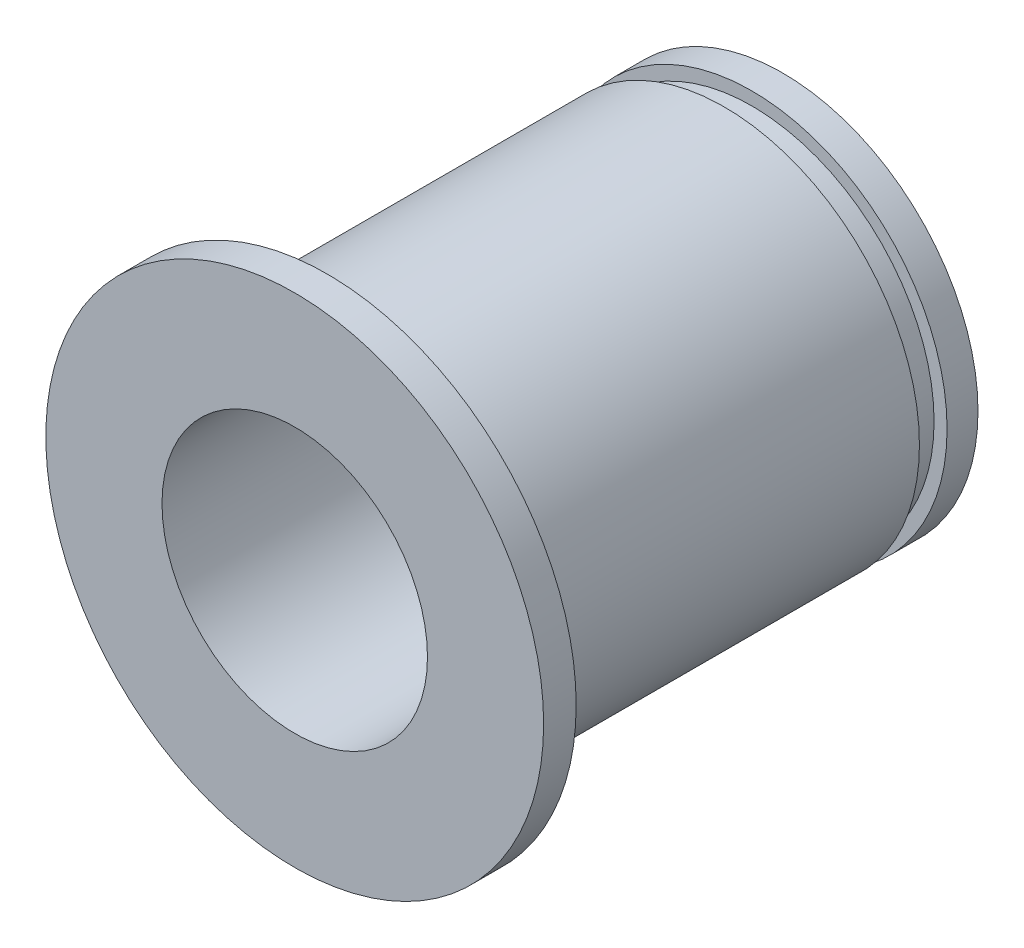
SolidWorks part; units mm, degrees
ref_plane "Front Plane" through (0, 0, 0) normal (0, 0, 1) x (1, 0, 0)
ref_plane "Top Plane" through (0, 0, 0) normal (0, 1, 0) x (1, 0, 0)
ref_plane "Right Plane" through (0, 0, 0) normal (1, 0, 0) x (0, 0, -1)
sketch "S01 - Ground guide bore and body" plane through (0, 0, 0) normal (0, 0, 1) x (1, 0, 0)
  circle A0 centre (0, 0) radius 6
  circle A1 centre (0, 0) radius 4.08
  dimension "D1" = 8.16
  dimension "D2" = 12
extrude "01 - Ground guide bore and body" add sketch "S01 - Ground guide bore and body" along normal blind 14 from offset 2 offset against normal yes
sketch "S02 - Outboard flange" plane through (0, 0, 0) normal (0, 0, 1) x (1, 0, 0)
  circle A0 centre (0, 0) radius 7.65
  circle A1 centre (0, 0) radius 4.08
  dimension "D1" = 8.16
  dimension "D2" = 15.3
extrude "02 - Outboard flange" add sketch "S02 - Outboard flange" along normal blind 1 from offset 12
sketch "S03 - External retaining ring groove" plane through (0, 0, 0) normal (0, 0, 1) x (1, 0, 0)
  circle A0 centre (0, 0) radius 6.1
  circle A1 centre (0, 0) radius 5.6
  dimension "D1" = 11.2
  dimension "D2" = 12.2
extrude "03 - External retaining ring groove" cut sketch "S03 - External retaining ring groove" along normal blind 0.85 from offset 1.05 offset against normal yes
